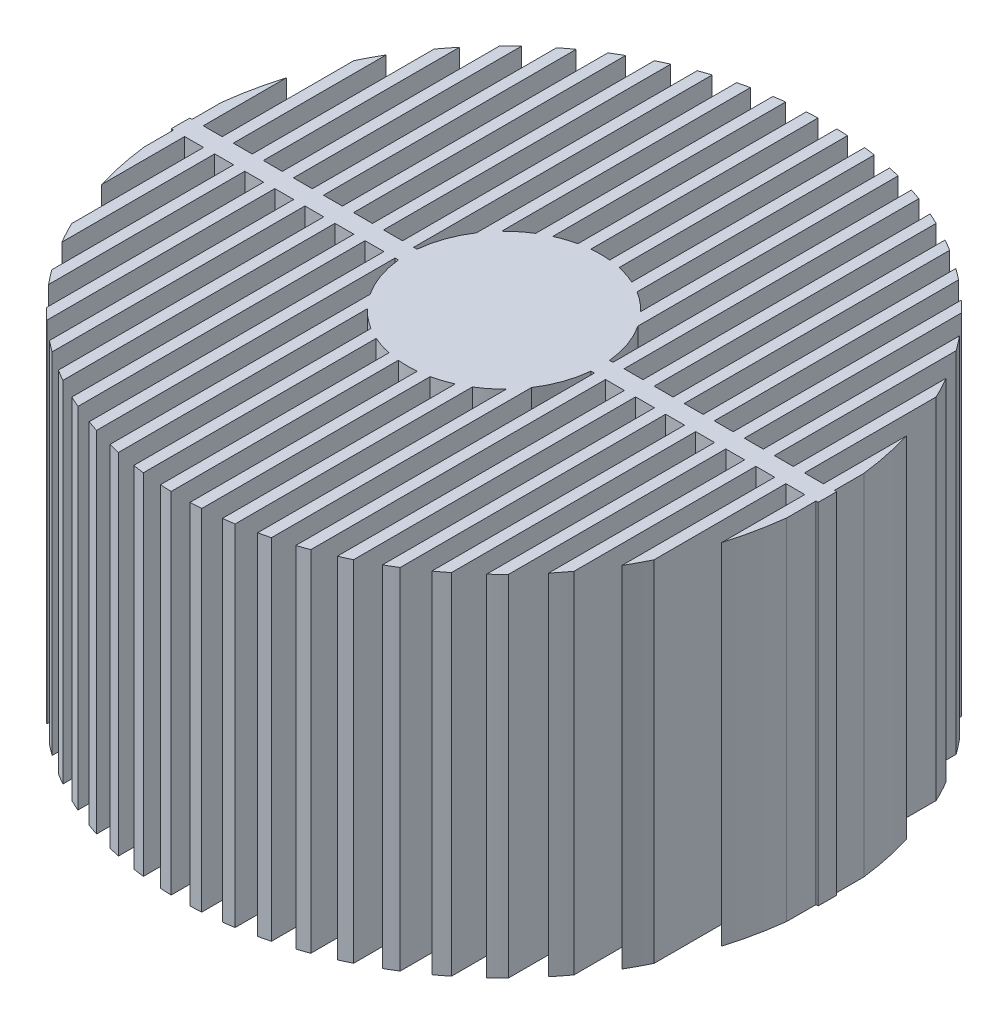
SolidWorks part; units mm, degrees
ref_plane "Alzado" through (0, 0, 0) normal (0, 0, 1) x (1, 0, 0)
ref_plane "Planta" through (0, 0, 0) normal (0, 1, 0) x (1, 0, 0)
ref_plane "Vista lateral" through (0, 0, 0) normal (1, 0, 0) x (0, 0, -1)
ref_axis "Eje1" through (14.3, 0, 0) along (-1, 0, 0)
sketch "Croquis3" plane through (0, 0, 0) normal (0, 1, 0) x (1, 0, 0)
  line L0 (0, 0) -> (0, 1.306) construction
  line L1 (-43.5, 1.25) -> (-12.9398, 1.25)
  line L2 (-43.5, 1.25) -> (-43.5, -1.25)
  line L3 (-43.5, -1.25) -> (-12.9398, -1.25)
  line L4 (43.5, 1.25) -> (43.5, -1.25)
  line L5 (0, 0) -> (1.811, 0) construction
  line L6 (14.3, 0) -> (-14.3, 0) construction
  line L7 (12.9398, 1.25) -> (43.5, 1.25)
  line L8 (12.9398, -1.25) -> (43.5, -1.25)
  arc A0 (-12.9398, -1.25) -> (12.9398, -1.25) centre (0, 0) ccw
  arc A1 (12.9398, 1.25) -> (-12.9398, 1.25) centre (0, 0) ccw
  point P9 (43.5, 0)
  dimension "D1" = 26
  dimension "D2" = 87
  dimension "D3" = 2.5
extrude "Saliente-Extruir3" add sketch "Croquis3" along normal blind 47 contours L3 A0 L8 L4 L7 A1 L1 L2
sketch "Croquis4" plane through (0, 47, 0) normal (0, 1, 0) x (1, 0, 0)
  line L0 (-43.5, 1.25) -> (-43.5, -1.25) construction
  line L1 (-43.1875, 43.5) -> (-41.6875, 43.5)
  line L2 (-43.1875, 43.5) -> (-43.1875, -43.5)
  line L3 (-43.1875, -43.5) -> (-41.6875, -43.5)
  line L4 (-41.6875, 43.5) -> (-41.6875, -43.5)
  line L5 (-39.1458, 43.5) -> (-39.1458, -43.5)
  line L6 (-39.1458, 43.5) -> (-37.6458, 43.5)
  line L7 (-37.6458, 43.5) -> (-37.6458, -43.5)
  line L8 (-39.1458, -43.5) -> (-37.6458, -43.5)
  line L9 (-35.104, 43.5) -> (-35.104, -43.5)
  line L10 (-35.104, 43.5) -> (-33.604, 43.5)
  line L11 (-33.604, 43.5) -> (-33.604, -43.5)
  line L12 (-35.104, -43.5) -> (-33.604, -43.5)
  line L13 (-31.0622, 43.5) -> (-31.0622, -43.5)
  line L14 (-31.0622, 43.5) -> (-29.5622, 43.5)
  line L15 (-29.5622, 43.5) -> (-29.5622, -43.5)
  line L16 (-31.0622, -43.5) -> (-29.5622, -43.5)
  line L17 (-27.0204, 43.5) -> (-27.0204, -43.5)
  line L18 (-27.0204, 43.5) -> (-25.5204, 43.5)
  line L19 (-25.5204, 43.5) -> (-25.5204, -43.5)
  line L20 (-27.0204, -43.5) -> (-25.5204, -43.5)
  line L21 (-22.9786, 43.5) -> (-22.9786, -43.5)
  line L22 (-22.9786, 43.5) -> (-21.4786, 43.5)
  line L23 (-21.4786, 43.5) -> (-21.4786, -43.5)
  line L24 (-22.9786, -43.5) -> (-21.4786, -43.5)
  line L25 (-18.9368, 43.5) -> (-18.9368, -43.5)
  line L26 (-18.9368, 43.5) -> (-17.4368, 43.5)
  line L27 (-17.4368, 43.5) -> (-17.4368, -43.5)
  line L28 (-18.9368, -43.5) -> (-17.4368, -43.5)
  line L29 (-14.895, 43.5) -> (-14.895, -43.5)
  line L30 (-14.895, 43.5) -> (-13.395, 43.5)
  line L31 (-13.395, 43.5) -> (-13.395, -43.5)
  line L32 (-14.895, -43.5) -> (-13.395, -43.5)
  line L33 (-10.8532, 43.5) -> (-10.8532, -43.5)
  line L34 (-10.8532, 43.5) -> (-9.3532, 43.5)
  line L35 (-9.3532, 43.5) -> (-9.3532, -43.5)
  line L36 (-10.8532, -43.5) -> (-9.3532, -43.5)
  line L37 (-6.8115, 43.5) -> (-6.8115, -43.5)
  line L38 (-6.8115, 43.5) -> (-5.3115, 43.5)
  line L39 (-5.3115, 43.5) -> (-5.3115, -43.5)
  line L40 (-6.8115, -43.5) -> (-5.3115, -43.5)
  line L41 (-2.7697, 43.5) -> (-2.7697, -43.5)
  line L42 (-2.7697, 43.5) -> (-1.2697, 43.5)
  line L43 (-1.2697, 43.5) -> (-1.2697, -43.5)
  line L44 (-2.7697, -43.5) -> (-1.2697, -43.5)
  line L45 (1.2721, 43.5) -> (1.2721, -43.5)
  line L46 (1.2721, 43.5) -> (2.7721, 43.5)
  line L47 (2.7721, 43.5) -> (2.7721, -43.5)
  line L48 (1.2721, -43.5) -> (2.7721, -43.5)
  line L49 (5.3139, 43.5) -> (5.3139, -43.5)
  line L50 (5.3139, 43.5) -> (6.8139, 43.5)
  line L51 (6.8139, 43.5) -> (6.8139, -43.5)
  line L52 (5.3139, -43.5) -> (6.8139, -43.5)
  line L53 (9.3557, 43.5) -> (9.3557, -43.5)
  line L54 (9.3557, 43.5) -> (10.8557, 43.5)
  line L55 (10.8557, 43.5) -> (10.8557, -43.5)
  line L56 (9.3557, -43.5) -> (10.8557, -43.5)
  line L57 (13.3975, 43.5) -> (13.3975, -43.5)
  line L58 (13.3975, 43.5) -> (14.8975, 43.5)
  line L59 (14.8975, 43.5) -> (14.8975, -43.5)
  line L60 (13.3975, -43.5) -> (14.8975, -43.5)
  line L61 (17.4393, 43.5) -> (17.4393, -43.5)
  line L62 (17.4393, 43.5) -> (18.9393, 43.5)
  line L63 (18.9393, 43.5) -> (18.9393, -43.5)
  line L64 (17.4393, -43.5) -> (18.9393, -43.5)
  line L65 (21.4811, 43.5) -> (21.4811, -43.5)
  line L66 (21.4811, 43.5) -> (22.9811, 43.5)
  line L67 (22.9811, 43.5) -> (22.9811, -43.5)
  line L68 (21.4811, -43.5) -> (22.9811, -43.5)
  line L69 (25.5228, 43.5) -> (25.5228, -43.5)
  line L70 (25.5228, 43.5) -> (27.0228, 43.5)
  line L71 (27.0228, 43.5) -> (27.0228, -43.5)
  line L72 (25.5228, -43.5) -> (27.0228, -43.5)
  line L73 (29.5646, 43.5) -> (29.5646, -43.5)
  line L74 (29.5646, 43.5) -> (31.0646, 43.5)
  line L75 (31.0646, 43.5) -> (31.0646, -43.5)
  line L76 (29.5646, -43.5) -> (31.0646, -43.5)
  line L77 (33.6064, 43.5) -> (33.6064, -43.5)
  line L78 (33.6064, 43.5) -> (35.1064, 43.5)
  line L79 (35.1064, 43.5) -> (35.1064, -43.5)
  line L80 (33.6064, -43.5) -> (35.1064, -43.5)
  line L81 (37.6482, 43.5) -> (37.6482, -43.5)
  line L82 (37.6482, 43.5) -> (39.1482, 43.5)
  line L83 (39.1482, 43.5) -> (39.1482, -43.5)
  line L84 (37.6482, -43.5) -> (39.1482, -43.5)
  line L85 (41.69, 43.5) -> (41.69, -43.5)
  line L86 (41.69, 43.5) -> (43.19, 43.5)
  line L87 (43.19, 43.5) -> (43.19, -43.5)
  line L88 (41.69, -43.5) -> (43.19, -43.5)
  line L89 (14.3, 0) -> (-14.3, 0) construction
  line L90 (43.5, 1.25) -> (43.5, -1.25) construction
  point P9 (-43.1875, 0)
  dimension "D1" = 1.5
  dimension "D3" = 0.31
  dimension "D4" = 0.3125
  dimension "D5" = 87
  dimension "D2" = 22
extrude "Saliente-Extruir4" add sketch "Croquis4" against normal blind 47
sketch "Croquis5" plane through (0, 47, 0) normal (0, 1, 0) x (1, 0, 0)
  circle A0 centre (0, 0) radius 43.5
extrude "Cortar-Extruir1" cut sketch "Croquis5" against normal blind 47 flip side to cut
sketch "Croquis6" [suppressed] plane through (0, 0, 0) normal (0, 1, 0) x (1, 0, 0)
  line L0 (1.8251, 43.4617) -> (1.8251, -43.4617)
  circle A0 centre (0, 0) radius 13
  circle A1 centre (0, 0) radius 43.5 construction
  dimension "D1" = 26
split line "Línea de partición1" [suppressed]
